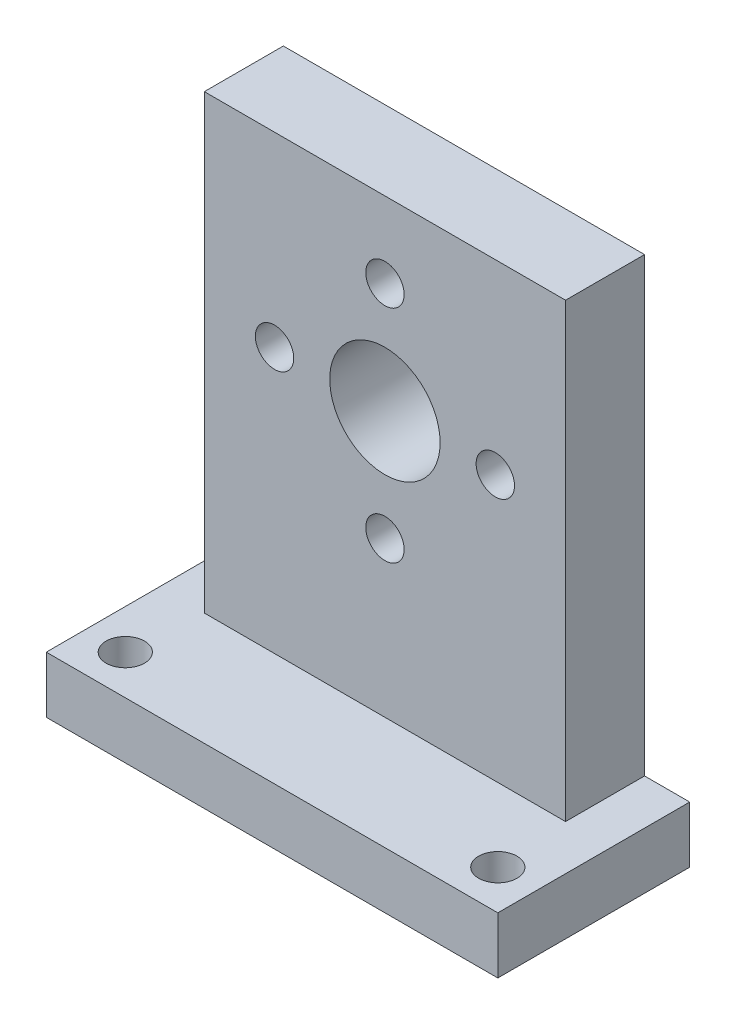
SolidWorks part; units mm, degrees
ref_plane "Front Plane" through (0, 0, 0) normal (0, 0, 1) x (1, 0, 0)
ref_plane "Top Plane" through (0, 0, 0) normal (0, 1, 0) x (1, 0, 0)
ref_plane "Right Plane" through (0, 0, 0) normal (1, 0, 0) x (0, 0, -1)
sketch "Sketch1" plane through (0, 0, 0) normal (0, 1, 0) x (1, 0, 0)
  line L1 (-20, 13.5) -> (20, 13.5)
  line L2 (-20, 13.5) -> (-20, -13.5)
  line L3 (-20, -13.5) -> (20, -13.5)
  line L4 (20, 13.5) -> (20, -13.5)
  line L5 (-20, 13.5) -> (20, -13.5) construction
  line L6 (-20, -13.5) -> (20, 13.5) construction
  line L7 (-16, 3.5) -> (16, 3.5)
  line L8 (-16, 3.5) -> (-16, -3.5)
  line L9 (-16, -3.5) -> (16, -3.5)
  line L10 (16, 3.5) -> (16, -3.5)
  line L11 (-16, 3.5) -> (16, -3.5) construction
  line L12 (-16, -3.5) -> (16, 3.5) construction
  point P0 (0, 0)
  point P6 (0, 0)
  dimension "D1" = 40
  dimension "D2" = 27
  dimension "D3" = 7
  dimension "D4" = 32
extrude "Boss-Extrude1" add sketch "Sketch1" along normal blind 5 contours L10 L7 L8 L9 | L2 L1 L4 L3 region at (0, 0, 0)
extrude "Boss-Extrude2" add sketch "Sketch1<3>" along normal blind 45 contours L10 L7 L8 L9 region at (0, 0, 0)
sketch "Sketch1<3>" plane through (0, 0, 0) normal (0, 1, 0) x (1, 0, 0) same geometry as "Sketch1"
sketch "Sketch2" plane through (0, 0, 3.5) normal (0, 0, 1) x (1, 0, 0)
  line L0 (-20, 5) -> (20, 5) construction
  circle A0 centre (0, 28.5) radius 4.8895
  dimension "D1" = 9.779
  dimension "D2" = 23.5
extrude "Cut-Extrude1" cut sketch "Sketch2" against normal up to next
sketch "Sketch4" plane through (0, 0, 3.5) normal (0, 0, 1) x (1, 0, 0)
  line L0 (0, 45) -> (0, 28.5) construction
  line L1 (-16, 45) -> (16, 45) construction
  circle A0 centre (0, 38.279) radius 1.7
  circle A1 centre (0, 28.5) radius 4.8895 construction
  circle A2 centre (9.779, 28.5) radius 1.7
  circle A3 centre (0, 18.721) radius 1.7
  circle A4 centre (-9.779, 28.5) radius 1.7
  circle A5 centre (0, 28.5) radius 9.779 construction
  point P18 (0, 28.5)
  dimension "D2" = 3.4
  dimension "D1" = 19.558
  dimension "D3" = 4
extrude "Cut-Extrude2" cut sketch "Sketch4" against normal up to next
sketch "Sketch5" plane through (0, 5, 0) normal (0, 1, 0) x (1, 0, 0)
  line L1 (-20, 13.5) -> (20, 13.5) construction
  line L2 (-20, 13.5) -> (-20, -13.5) construction
  line L3 (-20, -13.5) -> (20, -13.5) construction
  line L4 (0, 13.5) -> (0, -13.5) construction
  circle A0 centre (-16.5, 10) radius 1.7
  circle A2 centre (-16.5, -10) radius 1.7
  circle A4 centre (16.5, -10) radius 1.7
  circle A5 centre (16.5, 10) radius 1.7
  dimension "D3" = 3.4
  dimension "D1" = 3.5
  dimension "D2" = 3.5
  dimension "D4" = 3.5
extrude "Cut-Extrude3" cut sketch "Sketch5" against normal up to next
sketch "Sketch7" plane through (0, 5, 0) normal (0, 1, 0) x (1, 0, 0)
  line L0 (-20, 13.5) -> (-20, -13.5) construction
  line L1 (-20, 3.5) -> (20, 3.5)
  line L2 (-20, 3.5) -> (-20, 13.5)
  line L3 (-20, 13.5) -> (20, 13.5)
  line L4 (20, 3.5) -> (20, 13.5)
  line L5 (-16, 3.5) -> (16, 3.5) construction
extrude "Cut-Extrude5" cut sketch "Sketch7" against normal up to next
sketch "Sketch8" plane through (0, 0, -3.5) normal (0, 0, -1) x (-1, 0, 0)
  line L0 (-9.779, 28.5) -> (-9.779, 2.5) construction
  line L1 (0, 0) -> (0, 13.0763) construction
  line L5 (-20, 5) -> (-20, 0) construction
  circle A0 centre (-9.779, 2.5) radius 1.7
  circle A1 centre (9.779, 2.5) radius 1.7
  circle A2 centre (-9.779, 28.5) radius 1.7 construction
  point P9 (-20, 2.5)
extrude "Cut-Extrude6" cut sketch "Sketch8" against normal blind 6.35
